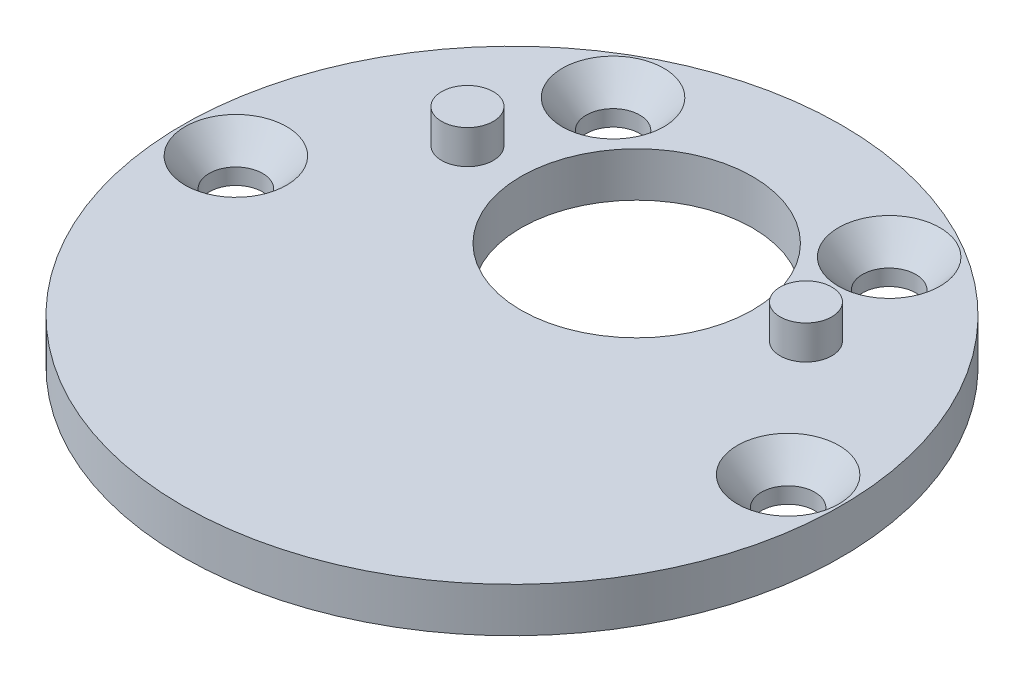
SolidWorks part; units mm, degrees
ref_plane "Front Plane" through (0, 0, 0) normal (0, 0, 1) x (1, 0, 0)
ref_plane "Top Plane" through (0, 0, 0) normal (0, 1, 0) x (1, 0, 0)
ref_plane "Right Plane" through (0, 0, 0) normal (1, 0, 0) x (0, 0, -1)
sketch "Sketch1" plane through (0, 0, 0) normal (0, 1, 0) x (1, 0, 0)
  line L4 (0, 0) -> (15.8817, 0) construction
  line L5 (0, 0) -> (0, 17.0912) construction
  line L6 (-7.75, 13.4234) -> (0, 0) construction
  line L7 (0, 0) -> (7.75, 13.4234) construction
  circle A0 centre (0, 0) radius 15.5 construction
  circle A1 centre (-7.75, 13.4234) radius 1.5
  circle A3 centre (-15.5, 0) radius 1.5
  circle A4 centre (7.75, 13.4234) radius 1.5
  circle A5 centre (15.5, 0) radius 1.5
  circle A6 centre (0, 0) radius 18.5
  dimension "D1" = 31
  dimension "D2" = 3
  dimension "D4" = 37
  dimension "D3" = 60
extrude "Boss-Extrude1" add sketch "Sketch1" along normal blind 2.5
sketch "Sketch2" plane through (0, 2.5, 0) normal (0, 1, 0) x (1, 0, 0)
  line L0 (0, 0) -> (0, 16.6144) construction
  line L1 (0, 0) -> (25.2906, 0) construction
  line L2 (-9.5, 7) -> (9.5, 7) construction
  circle A0 centre (-9.5, 7) radius 1.45
  circle A1 centre (9.5, 7) radius 1.45
  point P8 (0, 8.3072)
  point P11 (0, 7)
  dimension "D3" = 2.9
  dimension "D1" = 7
  dimension "D2" = 19
extrude "Boss-Extrude2" add sketch "Sketch2" along normal blind 1.9 and the other way blind 1
sketch "Sketch4" plane through (0, 2.5, 0) normal (0, 1, 0) x (1, 0, 0)
  line L0 (9.5, 7) -> (-9.5, 7) construction
  circle A0 centre (0, 7) radius 6.5
  dimension "D1" = 13
extrude "Cut-Extrude1" cut sketch "Sketch4" against normal through all
sketch "Sketch6" plane through (0, 2.5, 0) normal (0, 1, 0) x (1, 0, 0)
  line L0 (9.5, 7) -> (-9.5, 7) construction
  line L1 (0, 0) -> (0, 7) construction
  circle A0 centre (-9.5, 7) radius 2.7
  circle A1 centre (9.5, 7) radius 2.7
  circle A2 centre (-9.5, 7) radius 1.45 construction
  circle A3 centre (9.5, 7) radius 1.45
  circle A4 centre (-9.5, 7) radius 1.45
  circle A5 centre (9.5, 7) radius 1.45 construction
  dimension "D1" = 1.25
extrude "Cut-Extrude3" [suppressed] cut sketch "Sketch6" against normal blind 0.5
chamfer "Chamfer1" distance 1.35 distance2 1.6 4 edges at (-15.5, 2.5, 1.5) (15.5, 2.5, 1.5) (7.75, 2.5, -11.9234) (-7.75, 2.5, -11.9234) first distance on face at (0, 2.5, -0.5)
